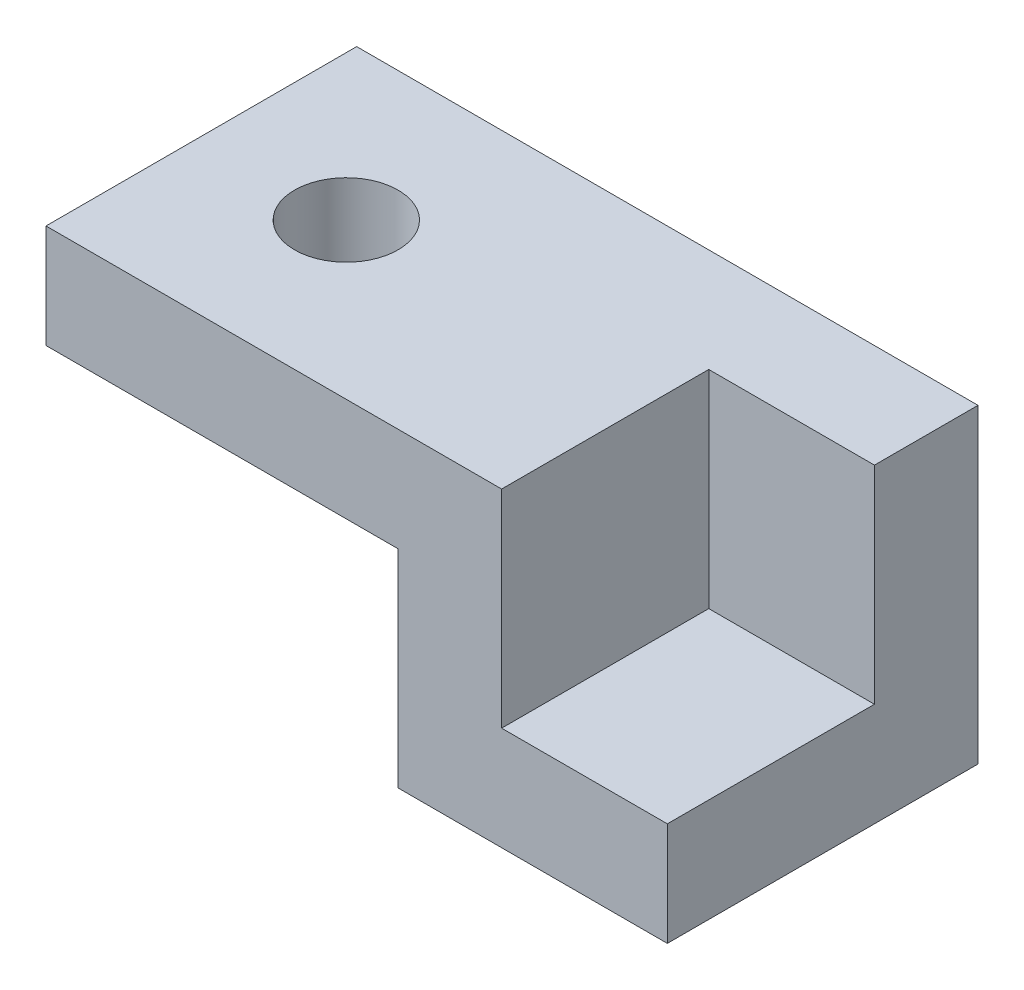
SolidWorks part; units mm, degrees
ref_plane "Front Plane" through (0, 0, 0) normal (0, 0, 1) x (1, 0, 0)
ref_plane "Top Plane" through (0, 0, 0) normal (0, 1, 0) x (1, 0, 0)
ref_plane "Right Plane" through (0, 0, 0) normal (1, 0, 0) x (0, 0, -1)
sketch "Sketch1" plane through (0, 0, 0) normal (0, 1, 0) x (1, 0, 0)
  line L0 (0, -25) -> (-40, -25)
  line L1 (0, 0) -> (-150, 0)
  line L2 (0, 0) -> (0, -75)
  line L3 (0, -75) -> (-150, -75)
  line L4 (-150, 0) -> (-150, -75)
  line L5 (-40, -25) -> (-40, -75)
  line L6 (-65, 0) -> (-65, -75)
  circle A0 centre (-115, -37.5) radius 12.5
  point P12 (-150, -37.5)
  dimension "D3" = 50
  dimension "D6" = 25
  dimension "D1" = 75
  dimension "D2" = 150
  dimension "D4" = 40
  dimension "D5" = 65
  dimension "D7" = 35
extrude "Boss-Extrude1" add sketch "Sketch1" along normal blind 25 from offset 50 contours L6 L1 L4 L3 A0 region at (-66.1336, 0, 37.5)
extrude "Boss-Extrude2" add sketch "Sketch1<3>" along normal blind 75 contours L1 L6 L3 L5 L0 L2 region at (-41.1957, 0, 28.8043)
sketch "Sketch1<3>" plane through (0, 0, 0) normal (0, 1, 0) x (1, 0, 0) same geometry as "Sketch1"
extrude "Boss-Extrude3" add sketch "Sketch1<4>" along normal blind 25 contours L0 L5 L3 L2 region at (-20, 0, 50)
sketch "Sketch1<4>" plane through (0, 0, 0) normal (0, 1, 0) x (1, 0, 0) same geometry as "Sketch1"
